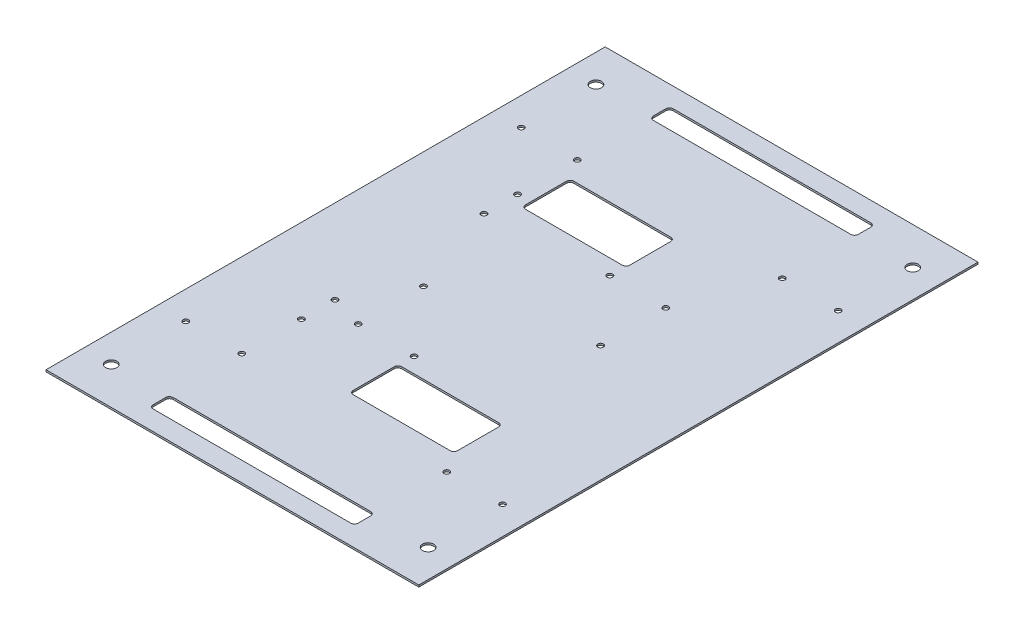
SolidWorks part; units mm, degrees
ref_plane "Plan de face" through (0, 0, 0) normal (0, 0, 1) x (1, 0, 0)
ref_plane "Plan de dessus" through (0, 0, 0) normal (0, 1, 0) x (1, 0, 0)
ref_plane "Plan de droite" through (0, 0, 0) normal (1, 0, 0) x (0, 0, -1)
sketch "Esquisse1" plane through (0, 0, 0) normal (0, 1, 0) x (1, 0, 0)
  line L0 (-2, -76.175) -> (42, -76.175) construction
  line L1 (-100, -150) -> (100, -150)
  line L2 (-100, -150) -> (-100, 150)
  line L3 (-100, 150) -> (100, 150)
  line L4 (100, -150) -> (100, 150)
  line L5 (-100, -150) -> (100, 150) construction
  line L6 (-100, 150) -> (100, -150) construction
  line L7 (-6, -53.175) -> (46, -53.175)
  line L8 (-8, -55.175) -> (-8, -77.175)
  line L9 (-6, -79.175) -> (46, -79.175)
  line L10 (48, -55.175) -> (48, -77.175)
  line L11 (47, -56.175) -> (-7, -56.175) construction
  line L12 (0, 0) -> (0, -150) construction
  line L13 (47, -150) -> (47, -53.175) construction
  line L14 (100, 0) -> (-100, 0) construction
  line L15 (-7, -53.175) -> (-7, -150) construction
  line L16 (0, 150) -> (0, 0) construction
  line L17 (7, 76.175) -> (-47, 76.175) construction
  line L18 (-46, 79.175) -> (6, 79.175)
  line L19 (-48, 77.175) -> (-48, 55.175)
  line L20 (-46, 53.175) -> (6, 53.175)
  line L21 (8, 77.175) -> (8, 55.175)
  line L22 (-47, 56.175) -> (7, 56.175) construction
  line L23 (-47, 56.175) -> (-47, 150) construction
  line L24 (-55, 0) -> (-55, 75.3308) construction
  line L25 (7, 56.175) -> (7, 150) construction
  line L26 (-53, -139.5001) -> (53, -139.5001)
  line L27 (55, -137.5001) -> (55, -130.7728)
  line L28 (53, -128.7728) -> (-53, -128.7728)
  line L29 (-60, -138.5001) -> (60, -138.5001) construction
  line L30 (57.5, -129.5001) -> (-57.5, -129.5001) construction
  line L31 (-55, -137.5001) -> (-55, -130.7728)
  line L32 (-55, 137.5001) -> (-55, 130.7728)
  line L33 (53, 128.7728) -> (-53, 128.7728)
  line L34 (55, 137.5001) -> (55, 130.7728)
  line L35 (-53, 139.5001) -> (53, 139.5001)
  arc A0 (46, -79.175) -> (48, -77.175) centre (46, -77.175) ccw
  arc A1 (48, -55.175) -> (46, -53.175) centre (46, -55.175) ccw
  arc A2 (-6, -53.175) -> (-8, -55.175) centre (-6, -55.175) ccw
  arc A3 (-8, -77.175) -> (-6, -79.175) centre (-6, -77.175) ccw
  arc A4 (8, 55.175) -> (6, 53.175) centre (6, 55.175) cw
  arc A5 (8, 77.175) -> (6, 79.175) centre (6, 77.175) ccw
  arc A6 (-46, 79.175) -> (-48, 77.175) centre (-46, 77.175) ccw
  arc A7 (-48, 55.175) -> (-46, 53.175) centre (-46, 55.175) ccw
  circle A8 centre (-37.5, -45) radius 1.5
  circle A9 centre (-7.5, -45) radius 1.5
  circle A10 centre (-37.5, -10) radius 1.5
  circle A11 centre (37.5, 10) radius 1.5
  circle A12 centre (37.5, 45) radius 1.5
  circle A13 centre (7.5, 45) radius 1.5
  circle A14 centre (85, 130) radius 3
  circle A15 centre (-85, 130) radius 3
  circle A16 centre (85, -130) radius 3
  circle A17 centre (-85, -130) radius 3
  circle A18 centre (-55, 40) radius 1.5
  circle A19 centre (-55, 58) radius 1.5
  circle A20 centre (-55, -58) radius 1.5
  circle A21 centre (-55, -40) radius 1.5
  arc A22 (53, -128.7728) -> (55, -130.7728) centre (53, -130.7728) cw
  arc A23 (53, -139.5001) -> (55, -137.5001) centre (53, -137.5001) ccw
  arc A24 (-55, -137.5001) -> (-53, -139.5001) centre (-53, -137.5001) ccw
  arc A25 (-55, -130.7728) -> (-53, -128.7728) centre (-53, -130.7728) cw
  arc A26 (-55, 130.7728) -> (-53, 128.7728) centre (-53, 130.7728) ccw
  arc A27 (-55, 137.5001) -> (-53, 139.5001) centre (-53, 137.5001) cw
  arc A28 (53, 128.7728) -> (55, 130.7728) centre (53, 130.7728) ccw
  arc A29 (53, 139.5001) -> (55, 137.5001) centre (53, 137.5001) cw
  circle A30 centre (-85, -90) radius 1.5
  circle A31 centre (-55, -90) radius 1.5
  circle A32 centre (85, -90) radius 1.5
  circle A33 centre (55, -90) radius 1.5
  circle A34 centre (55, 90) radius 1.5
  circle A35 centre (85, 90) radius 1.5
  circle A36 centre (-55, 90) radius 1.5
  circle A37 centre (-85, 90) radius 1.5
  point P0 (0, 0)
  point P93 (0, -139.5001)
  point P101 (0, -128.7728)
  point P107 (55, -128.7728)
  point P110 (55, -139.5001)
  point P113 (-55, -139.5001)
  point P116 (-55, -128.7728)
  point P119 (-55, 128.7728)
  point P122 (-55, 139.5001)
  point P125 (55, 128.7728)
  point P128 (55, 139.5001)
  dimension "D11" = 2
  dimension "D12" = 3
  dimension "D13" = 3
  dimension "D14" = 3
  dimension "D15" = 3
  dimension "D16" = 3
  dimension "D17" = 3
  dimension "D18" = 6
  dimension "D20" = 130
  dimension "D19" = 85
  dimension "D22" = 40
  dimension "D23" = 3
  dimension "D24" = 3
  dimension "D25" = 18
  dimension "D29" = 2
  dimension "D30" = 3
  dimension "D31" = 15
  dimension "D32" = 60
  dimension "D33" = 3
  dimension "D34" = 60
  dimension "D35" = 30
  dimension "D1" = 200
  dimension "D2" = 300
  dimension "D3" = 3
  dimension "D4" = 3
  dimension "D5" = 1
  dimension "D6" = 1
  dimension "D7" = 3
  dimension "D8" = 3
  dimension "D9" = 1
  dimension "D10" = 1
  dimension "D21" = 55
  dimension "D26" = 1
  dimension "D27" = 0.7272
  dimension "D28" = 55
extrude "Boss.-Extru.1" add sketch "Esquisse1" along normal blind 1
